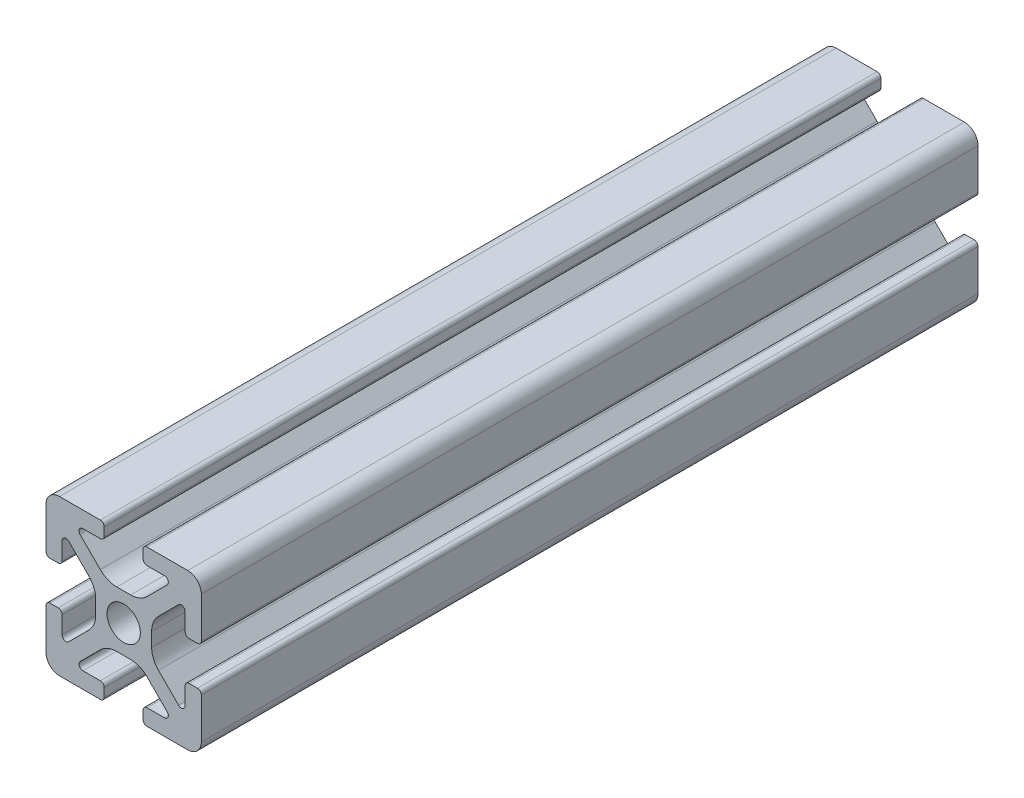
SolidWorks part; units mm, degrees
material "1060 Alloy"
ref_plane "Front Plane" through (0, 0, 0) normal (0, 0, 1) x (1, 0, 0)
ref_plane "Top Plane" through (0, 0, 0) normal (0, 1, 0) x (1, 0, 0)
ref_plane "Right Plane" through (0, 0, 0) normal (1, 0, 0) x (0, 0, -1)
sketch "Sketch2" plane through (0, 0, 0) normal (0, 0, 1) x (1, 0, 0)
  line L0 (0, 10) -> (0, -10) construction
  line L1 (-10, 0) -> (10, 0) construction
  line L2 (2.5, -10) -> (10, -10)
  line L3 (10, -10) -> (10, -2.5)
  line L4 (2.5, -10) -> (2.5, -7.9246)
  line L5 (2.5, -7.9246) -> (6.4571, -7.9246)
  line L6 (6.4571, -7.9246) -> (2.1325, -3.6)
  line L7 (0, 0) -> (10, -10) construction
  line L8 (10, -2.5) -> (7.9246, -2.5)
  line L9 (7.9246, -2.5) -> (7.9246, -6.4571)
  line L10 (7.9246, -6.4571) -> (3.6, -2.1325)
  line L11 (5.7623, -4.2948) -> (4.2948, -5.7623) construction
  circle A0 centre (0, 0) radius 2.15
  arc A1 (5.25, -7.9246) -> (5.6036, -7.0711) centre (5.25, -7.4246) ccw construction
  point P8 (0, -3.6)
  point P16 (5.0286, -5.0286)
  dimension "Center Hole Diameter" = 4.3
  dimension "D3" = 0.5
  dimension "Rail Height" = 20
  dimension "Rail Width" = 20
  dimension "T-Slot Width" = 5
  dimension "Slot Depth" = 6.4
  dimension "Slot Inner Width" = 11.5
sketch "Sketch3" plane through (0, 0, 0) normal (1, 0, 0) x (0, 0, -1)
  line L0 (-76.2, -10) -> (76.2, -10) construction
  line L1 (-50.8, 0) -> (50.8, 0) construction
  line L2 (0, 10) -> (0, -10) construction
  line L3 (0, 10) -> (0, -10) construction
  point P6 (-50.8, 0)
  point P8 (50.8, 0)
  dimension "Length" = 152.4
  dimension "D1" = 25.4
sketch "Sketch4" plane through (0, 0, 0) normal (0, 0, 1) x (1, 0, 0)
  line L0 (3, -10) -> (8.25, -10)
  line L1 (2.5, -10) -> (10, -10) construction
  line L2 (2.5, -10) -> (2.5, -7.9246) construction
  line L3 (2.5, -7.9246) -> (6.4571, -7.9246) construction
  line L4 (2.5, -8.4246) -> (2.5, -9.5)
  line L5 (3, -7.9246) -> (5.25, -7.9246)
  line L6 (0, -3.6) -> (0.8898, -3.6)
  line L7 (6.4571, -7.9246) -> (2.1325, -3.6) construction
  line L8 (3.0112, -4.4787) -> (5.6036, -7.0711)
  line L9 (10, -10) -> (10, -2.5) construction
  line L10 (7.9246, -6.4571) -> (3.6, -2.1325) construction
  line L11 (7.9246, -2.5) -> (7.9246, -6.4571) construction
  line L12 (7.9246, -5.25) -> (7.9246, -3)
  line L13 (10, -2.5) -> (7.9246, -2.5) construction
  line L14 (8.4246, -2.5) -> (9.5, -2.5)
  line L15 (10, -3) -> (10, -8.25)
  line L16 (7.0711, -5.6036) -> (4.4787, -3.0112)
  line L17 (3.6, 0) -> (3.6, -0.8898)
  line L18 (-10, 0) -> (10, 0) construction
  line L19 (0, -3.6) -> (0, -2.15)
  line L20 (0, 10) -> (0, -10) construction
  line L21 (3.6, 0) -> (2.15, 0)
  arc A0 (2.5, -9.5) -> (3, -10) centre (3, -9.5) ccw
  arc A1 (5.25, -7.9246) -> (5.6036, -7.0711) centre (5.25, -7.4246) ccw construction
  arc A2 (2.5, -8.4246) -> (3, -7.9246) centre (3, -8.4246) cw
  arc A3 (5.25, -7.9246) -> (5.6036, -7.0711) centre (5.25, -7.4246) ccw
  arc A4 (0.8898, -3.6) -> (3.0112, -4.4787) centre (0.8898, -6.6) cw
  arc A5 (8.25, -10) -> (10, -8.25) centre (8.25, -8.25) ccw
  arc A6 (7.0711, -5.6036) -> (7.9246, -5.25) centre (7.4246, -5.25) ccw
  arc A7 (7.9246, -3) -> (8.4246, -2.5) centre (8.4246, -3) cw
  arc A8 (9.5, -2.5) -> (10, -3) centre (9.5, -3) cw
  arc A9 (4.4787, -3.0112) -> (3.6, -0.8898) centre (6.6, -0.8898) cw
  circle A10 centre (0, 0) radius 2.15 construction
  arc A11 (0, -2.15) -> (2.15, 0) centre (0, 0) ccw
  dimension "D1" = 1.75
  dimension "D2" = 3
extrude "Boss-Extrude1" add sketch "Sketch4" along normal mid plane 152.4
mirror "Mirror1" about plane through (0, 0, 0) normal (1, 0, 0) of bodies 134
mirror "Mirror2" about plane through (0, 0, 0) normal (0, 1, 0) of bodies 135
sketch "Sketch5" plane through (0, 0, 76.2) normal (0, 0, 1) x (1, 0, 0)
  line L1 (-13.9539, 12.3566) -> (13.8334, 12.3566)
  line L2 (-13.9539, 12.3566) -> (-13.9539, -13.6827)
  line L3 (-13.9539, -13.6827) -> (13.8334, -13.6827)
  line L4 (13.8334, 12.3566) -> (13.8334, -13.6827)
extrude "Cut-Extrude1" cut sketch "Sketch5" against normal blind 52.4
sketch "Sketch7" plane through (0, 10, 0) normal (0, 1, 0) x (1, 0, 0)
  line L1 (-10, -23.8) -> (-10, 76.2) construction
  line L2 (8.25, -23.8) -> (3, -23.8) construction
  circle A0 centre (0, 26.2) radius 2.55
  circle A1 centre (0, 46.2) radius 2.55
  circle A2 centre (0, 6.2) radius 2.55
  dimension "D3" = 5.1
  dimension "D6" = 5.1
  dimension "D7" = 5.1
  dimension "D1" = 10
  dimension "D2" = 50
  dimension "D4" = 20
  dimension "D5" = 20
equation "\"D3@Sketch2\"=\"T-Slot Width@Sketch2\"*0.1"
equation "\"D1@Sketch4\"=\"D3@Sketch2\"*3.5"
equation "\"D2@Sketch4\"=\"D3@Sketch2\"*6"
equation "\"D1@Boss-Extrude1\"=\"Length@Sketch3\""
